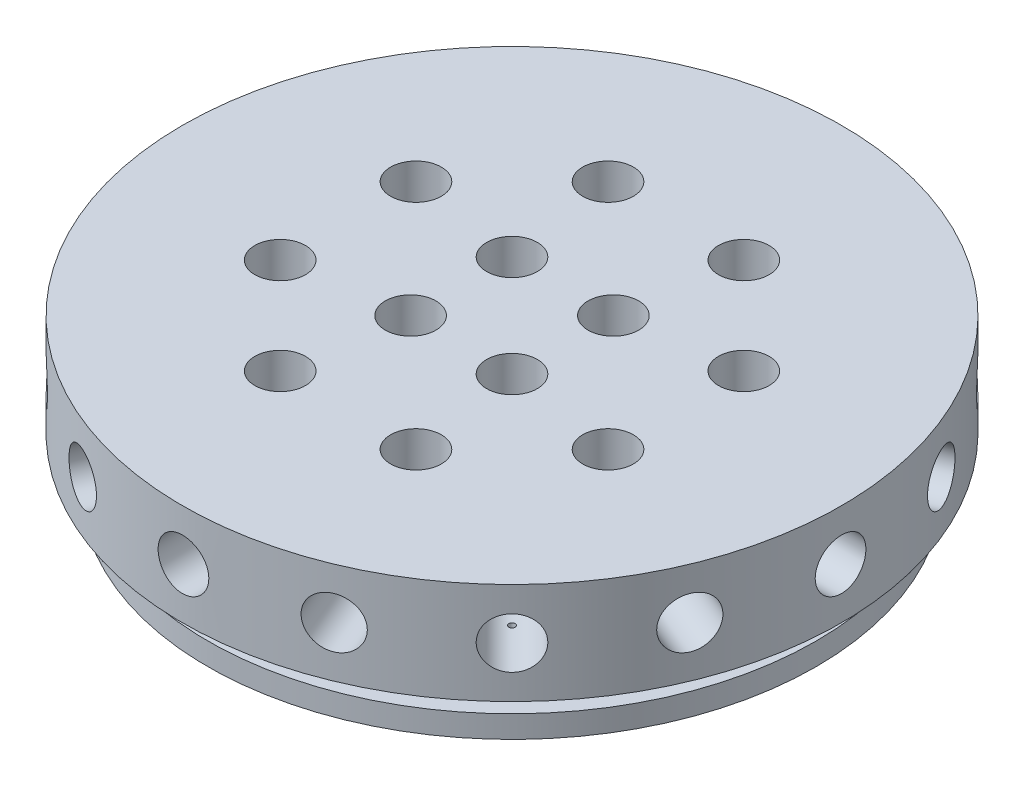
SolidWorks part; units mm, degrees
ref_plane "Front Plane" through (0, 0, 0) normal (0, 0, 1) x (1, 0, 0)
ref_plane "Top Plane" through (0, 0, 0) normal (0, 1, 0) x (1, 0, 0)
ref_plane "Right Plane" through (0, 0, 0) normal (1, 0, 0) x (0, 0, -1)
ref_axis "Axis1" through (0, -42.3, 0) along (0, 1, 0)
sketch "Sketch1" plane through (0, 0, 0) normal (0, 0, 1) x (1, 0, 0)
  line L0 (0, 0) -> (-38.1, 0)
  line L1 (-38.1, 0) -> (-38.1, 2.7877)
  line L2 (-38.1, 2.7877) -> (-36.068, 2.7877)
  line L3 (-36.068, 2.7877) -> (-36.068, 5.5563)
  line L4 (-36.068, 5.5563) -> (-38.1, 5.5563)
  line L5 (-38.1, 5.5563) -> (-38.1, 6.35)
  line L6 (-38.1, 6.35) -> (-41.275, 6.35)
  line L7 (-41.275, 6.35) -> (-41.275, 19.05)
  line L10 (-41.275, 19.05) -> (0, 19.05)
  line L11 (0, 19.05) -> (0, 0)
  dimension "D1" = 38.1
  dimension "D2" = 2.7686
  dimension "D3" = 12.7
  dimension "D4" = 0.7937
  dimension "D5" = 2.032
  dimension "D6" = 3.175
  dimension "D9" = 19.05
revolve "Revolve1" add sketch "Sketch1" angle 360 about L11
ref_plane "Plane1" through (41.275, 0, 0) normal (1, 0, 0) x (0, 0, -1)
hole_wizard "1/4 (0.25) Diameter Hole1" positions "Sketch12" profile "Sketch13" hole size "1/4" standard "ANSI Inch"
sketch "Sketch12" plane through (41.275, 0, 0) normal (1, 0, 0) x (0, 0, -1)
  point P0 (0, 12.7)
  dimension "D1" = 12.7
sketch "Sketch13" plane through (41.275, 12.7, 0) normal (0, 1, 0) x (0, 0, -1)
  line L0 (0, 0) -> (0, 14.6077)
  line L1 (0, 14.6077) -> (3.175, 12.7)
  line L2 (3.175, 12.7) -> (3.175, 0)
  line L5 (3.175, 0) -> (0, 0)
  line L10 (0, 14.6077) -> (-3.175, 12.7) construction
  line L11 (0, -6.35) -> (0, 107.95) construction
  dimension "Hole Dia." = 6.35
  dimension "Hole Depth" = 12.7
  dimension "Drill Angle" = 118
hole_wizard "3/16 (0.1875) Diameter Hole1" positions "Sketch14" profile "Sketch15" hole size "3/16" standard "ANSI Inch"
sketch "Sketch14" plane through (41.275, 0, 0) normal (1, 0, 0) x (0, 0, -1)
  point P0 (0, 12.7)
sketch "Sketch15" plane through (41.275, 12.7, 0) normal (0, 1, 0) x (0, 0, -1)
  line L0 (0, 0) -> (0, 26.8308)
  line L1 (0, 26.8308) -> (2.3812, 25.4)
  line L2 (2.3812, 25.4) -> (2.3812, 0)
  line L5 (2.3812, 0) -> (0, 0)
  line L10 (0, 26.8308) -> (-2.3813, 25.4) construction
  line L11 (0, -6.35) -> (0, 107.95) construction
  dimension "Hole Dia." = 4.7625
  dimension "Hole Depth" = 25.4
  dimension "Drill Angle" = 118
hole_wizard "1/8 (0.125) Diameter Hole1" positions "Sketch16" profile "Sketch17" hole size "1/8" standard "ANSI Inch"
sketch "Sketch16" plane through (41.275, 0, 0) normal (1, 0, 0) x (0, 0, -1)
  point P0 (0, 12.7)
sketch "Sketch17" plane through (41.275, 12.7, 0) normal (0, 1, 0) x (0, 0, -1)
  line L0 (0, 0) -> (0, 35.8789)
  line L1 (0, 35.8789) -> (1.5875, 34.925)
  line L2 (1.5875, 34.925) -> (1.5875, 0)
  line L5 (1.5875, 0) -> (0, 0)
  line L10 (0, 35.8789) -> (-1.5875, 34.925) construction
  line L11 (0, -6.35) -> (0, 107.95) construction
  dimension "Hole Dia." = 3.175
  dimension "Hole Depth" = 34.925
  dimension "Drill Angle" = 118
pattern_circular "CirPattern1" count 16 over 360 about axis through (0, -42.3, 0) along (0, 1, 0) of "1/4 (0.25) Diameter Hole1"
pattern_circular "CirPattern2" count 8 over 360 about axis through (0, -42.3, 0) along (0, 1, 0) of "3/16 (0.1875) Diameter Hole1"
pattern_circular "CirPattern3" count 4 over 360 about axis through (0, -42.3, 0) along (0, 1, 0) of "1/8 (0.125) Diameter Hole1"
ref_plane "Plane2" through (0, 19.05, 0) normal (0, 1, 0) x (1, 0, 0)
hole_wizard "inner large LOX holes" positions "Sketch19" profile "Sketch20" hole size "1/4" standard "ANSI Inch"
sketch "Sketch19" plane through (0, 19.05, 0) normal (0, 1, 0) x (1, 0, 0)
  line L2 (-6.35, 0) -> (0, 0) construction
  line L4 (-6.35, -6.35) -> (-6.35, 0) construction
  point P0 (-6.35, -6.35)
  dimension "D1" = 6.35
  dimension "D2" = 6.35
sketch "Sketch20" plane through (-6.35, 19.05, 6.35) normal (1, 0, 0) x (0, 0, 1)
  line L0 (0, 0) -> (0, 14.6077)
  line L1 (0, 14.6077) -> (3.175, 12.7)
  line L2 (3.175, 12.7) -> (3.175, 0)
  line L5 (3.175, 0) -> (0, 0)
  line L10 (0, 14.6077) -> (-3.175, 12.7) construction
  line L11 (0, -6.35) -> (0, 107.95) construction
  dimension "Hole Dia." = 6.35
  dimension "Hole Depth" = 12.7
  dimension "Drill Angle" = 118
hole_wizard "outer large LOX hole" positions "Sketch21" profile "Sketch22" hole size "1/4" standard "ANSI Inch"
sketch "Sketch21" plane through (0, 19.05, 0) normal (0, 1, 0) x (1, 0, 0)
  line L0 (-20.5332, -8.5051) -> (0, 0) construction
  line L2 (0, 0) -> (-17.5003, 0) construction
  point P0 (-20.5332, -8.5051)
  dimension "D1" = 22.5
  dimension "D2" = 22.225
sketch "Sketch22" plane through (-20.5332, 19.05, 8.5051) normal (1, 0, 0) x (0, 0, 1)
  line L0 (0, 0) -> (0, 14.6077)
  line L1 (0, 14.6077) -> (3.175, 12.7)
  line L2 (3.175, 12.7) -> (3.175, 0)
  line L5 (3.175, 0) -> (0, 0)
  line L10 (0, 14.6077) -> (-3.175, 12.7) construction
  line L11 (0, -6.35) -> (0, 107.95) construction
  dimension "Hole Dia." = 6.35
  dimension "Hole Depth" = 12.7
  dimension "Drill Angle" = 118
pattern_circular "CirPattern4" count 4 over 360 about axis through (0, -42.3, 0) along (0, 1, 0) of "inner large LOX holes"
pattern_circular "CirPattern5" count 8 over 360 about axis through (0, -42.3, 0) along (0, 1, 0) of "outer large LOX hole"
ref_plane "Plane4" through (-34.925, 0, 0) normal (1, 0, 0) x (0, 0, -1)
ref_axis "Axis4" through (-34.925, 0, -45.4025) along (0, 0, 1)
ref_plane "Plane5" through (-0.2653, -3.0323, 0) normal (0.0872, 0.9962, 0) x (0, 0, 1)
ref_plane "Plane6" through (-0.4037, -4.6138, 0) normal (0.0872, 0.9962, 0) x (0, 0, 1)
hole_wizard "film cooling holes" positions "Sketch25" profile "Sketch26" hole size "1/32" standard "ANSI Inch"
sketch "Sketch25" plane through (-0.4037, -4.6138, 0) normal (0.0872, 0.9962, 0) x (0, 0, 1)
  line L0 (0, -34.7921) -> (0, 0) construction
  line L1 (-45.4025, -34.7921) -> (45.4025, -34.7921) construction
  point P0 (0, -34.7921)
sketch "Sketch26" plane through (-35.0634, -1.5815, 0) normal (0, 0, 1) x (0.9962, -0.0872, 0)
  line L0 (0, 0) -> (0, 12.9385)
  line L1 (0, 12.9385) -> (0.3969, 12.7)
  line L2 (0.3969, 12.7) -> (0.3969, 0)
  line L5 (0.3969, 0) -> (0, 0)
  line L10 (0, 12.9385) -> (-0.3969, 12.7) construction
  line L11 (0, -6.35) -> (0, 107.95) construction
  dimension "Hole Dia." = 0.7937
  dimension "Hole Depth" = 12.7
  dimension "Drill Angle" = 118
pattern_circular "CirPattern6" count 16 over 360 about axis through (0, -42.3, 0) along (0, 1, 0) of "film cooling holes"
hole_wizard "1/32 (0.03125) Diameter Hole3" positions "Sketch27" profile "Sketch28" hole size "1/32" standard "ANSI Inch"
sketch "Sketch27" plane through (0, 0, 0) normal (0, 1, 0) x (1, 0, 0)
  point P0 (-6.35, 0)
  dimension "D1" = 6.35
sketch "Sketch28" plane through (-6.35, 0, 0) normal (1, 0, 0) x (0, 0, -1)
  line L0 (0, 0) -> (0, 12.9385)
  line L1 (0, 12.9385) -> (0.3969, 12.7)
  line L2 (0.3969, 12.7) -> (0.3969, 0)
  line L5 (0.3969, 0) -> (0, 0)
  line L10 (0, 12.9385) -> (-0.3969, 12.7) construction
  line L11 (0, -6.35) -> (0, 107.95) construction
  dimension "Hole Dia." = 0.7937
  dimension "Hole Depth" = 12.7
  dimension "Drill Angle" = 118
ref_axis "Axis2" through (0, 19.05, -45.4025) along (0, 0, 1)
ref_axis "Axis3" through (45.4025, 19.05, 0) along (-1, 0, 0)
